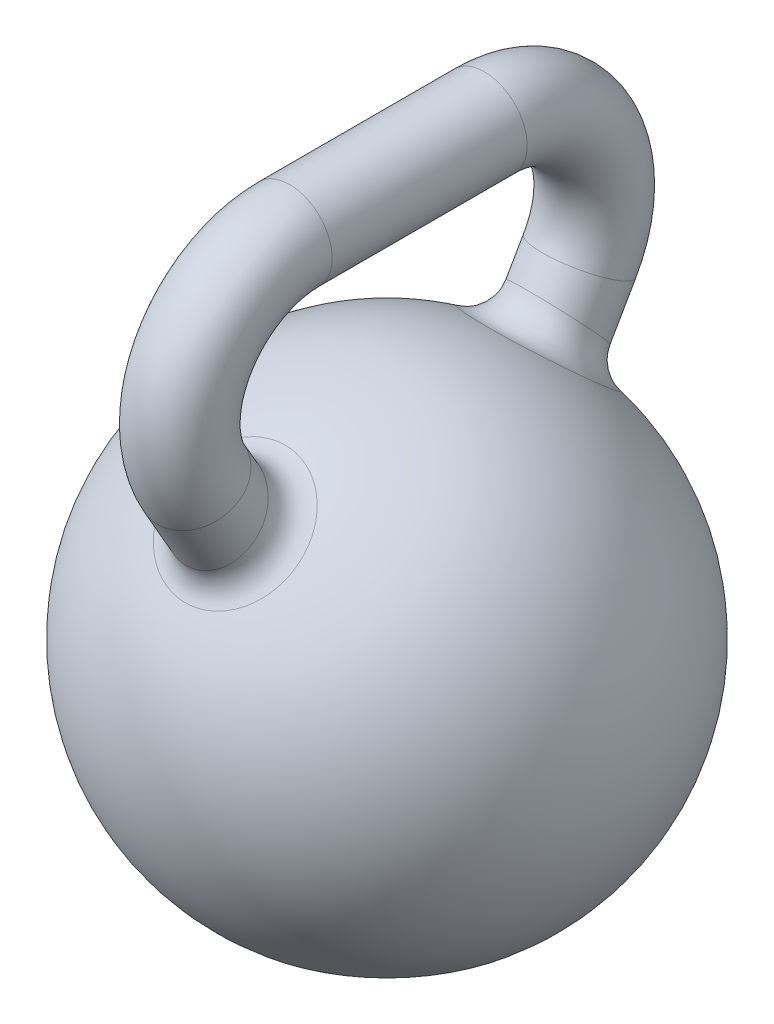
SolidWorks part; units mm, degrees
material "Gray Cast Iron"
ref_plane "Front Plane" through (0, 0, 0) normal (0, 0, 1) x (1, 0, 0)
ref_plane "Top Plane" through (0, 0, 0) normal (0, 1, 0) x (1, 0, 0)
ref_plane "Right Plane" through (0, 0, 0) normal (1, 0, 0) x (0, 0, -1)
sketch "Sketch1" plane through (0, 0, 0) normal (0, 0, 1) x (1, 0, 0)
  line L0 (0, -77.47) -> (63.7535, -77.47)
  line L1 (0, -77.47) -> (0, 100.33)
  arc A0 (63.7535, -77.47) -> (0, 100.33) centre (0, 0) ccw
  dimension "D1" = 100.33
  dimension "D2" = 77.47
revolve "Revolve1" add sketch "Sketch1" angle 360 about L1
sketch "Sketch2" plane through (0, 0, 0) normal (1, 0, 0) x (0, 0, -1)
  line L0 (-63.5, 33.2447) -> (-95.6326, 88.9)
  line L1 (-40.64, 184.15) -> (40.64, 184.15)
  line L2 (95.6326, 88.9) -> (63.5, 33.2447)
  arc A0 (63.7535, -77.47) -> (-63.7535, -77.47) centre (0, 0) ccw construction
  arc A1 (-95.6326, 88.9) -> (-40.64, 184.15) centre (-40.64, 120.65) cw
  arc A2 (40.64, 184.15) -> (95.6326, 88.9) centre (40.64, 120.65) cw
  arc A3 (63.7535, -77.47) -> (-63.7535, -77.47) centre (0, 0) ccw construction
  point P10 (0, 0)
  point P12 (0, 184.15)
  point P13 (87.9117, 48.3491)
  point P14 (0, 0)
  point P15 (87.0147, 49.9455)
  point P16 (0, 0)
  point P17 (60.2898, 37.8002)
  point P18 (67.2665, 39.7685)
  dimension "D1" = 63.5
  dimension "D2" = 81.28
  dimension "D3" = 184.15
  dimension "D4" = 60
  dimension "D5" = 63.5
sketch "Sketch42" plane through (0, 0, 0) normal (0, 0, 1) x (1, 0, 0)
  circle A0 centre (0, 166.37) radius 17.78
  point P2 (0, 0)
  point P4 (0, 0)
  dimension "D2" = 35.56
  dimension "D1" = 184.15
sweep "Sweep2" add profiles "Sketch42" path "Sketch2"
fillet "Fillet2" radius 12.7 2 edges at (9.5692, 83.5534, -54.7117) (5.9167, 84.7621, 53.3525)
